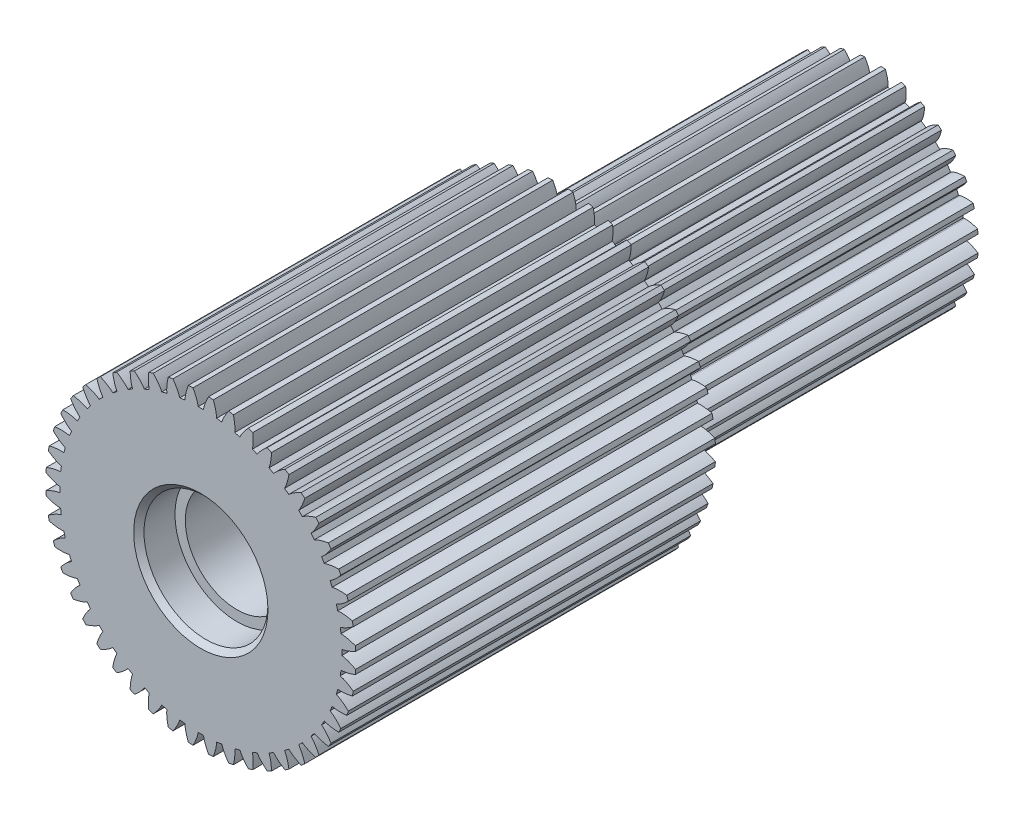
SolidWorks part; units mm, degrees
material "PLA"
ref_plane "Front Plane" through (0, 0, 0) normal (0, 0, 1) x (1, 0, 0)
ref_plane "Top Plane" through (0, 0, 0) normal (0, 1, 0) x (1, 0, 0)
ref_plane "Right Plane" through (0, 0, 0) normal (1, 0, 0) x (0, 0, -1)
sketch "Sketch1" plane through (0, 0, 0) normal (0, 0, 1) x (1, 0, 0)
  circle A0 centre (0, 0) radius 15
  dimension "D1" = 30
extrude "Boss-Extrude1" add sketch "Sketch1" along normal mid plane 34.8118
sketch "Sketch2" plane through (0, 0, 0) normal (0, 0, 1) x (1, 0, 0)
  line L0 (0, 0) -> (14.3977, 0.2566) construction
  line L1 (0, 0) -> (14.4, 0) construction
  line L2 (0, 0) -> (14.3977, -0.2566) construction
  line L3 (13.527, -0.2411) -> (13.6478, -0.2432)
  line L4 (13.5294, 0.2411) -> (13.6478, 0.2432)
  circle A0 centre (0, 0) radius 14.4 construction
  circle A1 centre (0, 0) radius 13.5316 construction
  circle A2 centre (0, 0) radius 13.65
  circle A3 centre (0, 0) radius 15 construction
  circle A4 centre (0, 0) radius 15
  spline S0 degree 4 poles (13.5294, 0.2411) (13.534, 0.2413) (13.547, 0.2419) (13.5715, 0.2439) (13.6113, 0.2483) (13.662, 0.2556) (13.7273, 0.267) (13.8039, 0.2829) (13.8878, 0.303) (13.9786, 0.3276) (14.0688, 0.3547) (14.1584, 0.3839) (14.2472, 0.4152) (14.3542, 0.4554) (14.4819, 0.507) (14.6298, 0.5722) (14.7962, 0.6518) (14.964, 0.7391) (15.1277, 0.8299) (15.2913, 0.9272) (15.4482, 1.0254) (15.6092, 1.1331) (15.7568, 1.2354) (15.9198, 1.3563) (16.0506, 1.4557) (16.2205, 1.5933) (16.32, 1.6765) (16.4355, 1.7761) (16.4863, 1.8215) (16.5176, 1.8494) knots 0 0 0 0 0 0.005377 0.015084 0.028532 0.04661 0.064855 0.092111 0.119476 0.146842 0.174209 0.201575 0.228941 0.256307 0.307035 0.361767 0.4165 0.471232 0.525964 0.580697 0.635429 0.690161 0.744894 0.799626 0.854358 0.909091 0.954545 1 1 1 1 1 construction
  spline S1 degree 4 poles (13.5294, 0.2411) (13.534, 0.2413) (13.547, 0.2419) (13.5715, 0.2439) (13.6113, 0.2483) (13.662, 0.2556) (13.7273, 0.267) (13.8039, 0.2829) (13.8878, 0.303) (13.9786, 0.3276) (14.0688, 0.3547) (14.1584, 0.3839) (14.2472, 0.4152) (14.3542, 0.4554) (14.4819, 0.507) (14.6298, 0.5722) (14.7962, 0.6518) (14.964, 0.7391) (15.1277, 0.8299) (15.2913, 0.9272) (15.4482, 1.0254) (15.6092, 1.1331) (15.7568, 1.2354) (15.9198, 1.3563) (16.0506, 1.4557) (16.1836, 1.5634) (16.2481, 1.6166) (16.2809, 1.6441) knots 0 0 0 0 0 0.005377 0.015084 0.028532 0.04661 0.064855 0.092111 0.119476 0.146842 0.174209 0.201575 0.228941 0.256307 0.307035 0.361767 0.4165 0.471232 0.525964 0.580697 0.635429 0.690161 0.744894 0.799626 0.854358 0.909091 0.909091 0.909091 0.909091 0.909091
  spline S2 degree 4 poles (13.527, -0.2411) (13.5316, -0.2412) (13.5446, -0.2419) (13.569, -0.2438) (13.6089, -0.2483) (13.6595, -0.2556) (13.7248, -0.2669) (13.8015, -0.2828) (13.8853, -0.3029) (13.9762, -0.3276) (14.0664, -0.3546) (14.1559, -0.3839) (14.2447, -0.4151) (14.3518, -0.4554) (14.4794, -0.507) (14.6274, -0.5722) (14.7937, -0.6518) (14.9616, -0.739) (15.1253, -0.8298) (15.2888, -0.9272) (15.4458, -1.0254) (15.6068, -1.1331) (15.7543, -1.2354) (15.9173, -1.3563) (16.0481, -1.4556) (16.218, -1.5932) (16.3175, -1.6764) (16.4331, -1.776) (16.4838, -1.8215) (16.5151, -1.8494) knots 0 0 0 0 0 0.005377 0.015084 0.028532 0.04661 0.064855 0.092111 0.119476 0.146842 0.174209 0.201575 0.228941 0.256307 0.307035 0.361767 0.4165 0.471232 0.525964 0.580697 0.635429 0.690161 0.744894 0.799626 0.854358 0.909091 0.954545 1 1 1 1 1 construction
  spline S3 degree 4 poles (13.527, -0.2411) (13.5316, -0.2412) (13.5446, -0.2419) (13.569, -0.2438) (13.6089, -0.2483) (13.6595, -0.2556) (13.7248, -0.2669) (13.8015, -0.2828) (13.8853, -0.3029) (13.9762, -0.3276) (14.0664, -0.3546) (14.1559, -0.3839) (14.2447, -0.4151) (14.3518, -0.4554) (14.4794, -0.507) (14.6274, -0.5722) (14.7937, -0.6518) (14.9616, -0.739) (15.1253, -0.8298) (15.2888, -0.9272) (15.4458, -1.0254) (15.6068, -1.1331) (15.7543, -1.2354) (15.9173, -1.3563) (16.0481, -1.4556) (16.1812, -1.5634) (16.2456, -1.6166) (16.2784, -1.6441) knots 0 0 0 0 0 0.005377 0.015084 0.028532 0.04661 0.064855 0.092111 0.119476 0.146842 0.174209 0.201575 0.228941 0.256307 0.307035 0.361767 0.4165 0.471232 0.525964 0.580697 0.635429 0.690161 0.744894 0.799626 0.854358 0.909091 0.909091 0.909091 0.909091 0.909091
  dimension "D1" = 28.8
  dimension "D2" = 27.0631
  dimension "D3" = 27.3
  dimension "D4" = 1.021
  dimension "D5" = 1.021
extrude "Cut-Extrude1" cut sketch "Sketch2" against normal through all both and the other way through all contours A2 A4 region at (14.4443, -0.0005, 0)
pattern_circular "CirPattern2" count 48 over 360 about axis through (0, 0, 17.4059) along (0, 0, -1) of "Cut-Extrude1"
sketch "Sketch3" plane through (0, 0, 17.4059) normal (0, 0, 1) x (1, 0, 0)
  circle A0 centre (0, 0) radius 5
  dimension "D1" = 10
sketch "Sketch4" plane through (0, 0, -17.4059) normal (0, 0, -1) x (-1, 0, 0)
  circle A0 centre (0, 0) radius 10.2
  dimension "D1" = 20.4
extrude "Boss-Extrude2" add sketch "Sketch4" along normal blind 30.2315
sketch "Sketch5" plane through (0, 0, -47.6374) normal (0, 0, -1) x (-1, 0, 0)
  line L0 (0, 0) -> (10.2, 0) construction
  line L1 (0, 0) -> (10.194, 0.3486) construction
  line L2 (0, 0) -> (10.194, -0.3486) construction
  line L3 (8.9952, 0.3076) -> (8.8448, 0.3025)
  line L4 (8.9952, -0.3076) -> (8.8448, -0.3025)
  circle A0 centre (0, 0) radius 9.021 construction
  circle A1 centre (0, 0) radius 8.85
  arc A2 (10.1694, -0.7895) -> (10.1694, 0.7895) centre (0, 0) ccw
  spline S0 degree 4 poles (8.9952, 0.3076) (8.9983, 0.3078) (9.0069, 0.3083) (9.0232, 0.3099) (9.0497, 0.3133) (9.0989, 0.3212) (9.1575, 0.3334) (9.2234, 0.3498) (9.2937, 0.3702) (9.3535, 0.3892) (9.4129, 0.4097) (9.4717, 0.4314) (9.5427, 0.4594) (9.6272, 0.4952) (9.7251, 0.5403) (9.8351, 0.5952) (9.9461, 0.6552) (10.0542, 0.7175) (10.1621, 0.7842) (10.2657, 0.8513) (10.3718, 0.9249) (10.4691, 0.9947) (10.5764, 1.077) (10.6625, 1.1447) (10.7743, 1.2383) (10.8397, 1.2948) (10.9156, 1.3625) (10.9489, 1.3933) (10.9695, 1.4123) knots 0 0 0 0 0 0.005377 0.015084 0.028532 0.04661 0.092111 0.119476 0.146842 0.174209 0.201575 0.228941 0.256307 0.307035 0.361767 0.4165 0.471232 0.525964 0.580697 0.635429 0.690161 0.744894 0.799626 0.854358 0.909091 0.954545 1 1 1 1 1 construction
  spline S1 degree 4 poles (8.9952, 0.3076) (8.9983, 0.3078) (9.0069, 0.3083) (9.0232, 0.3099) (9.0497, 0.3133) (9.0989, 0.3212) (9.1575, 0.3334) (9.2234, 0.3498) (9.2937, 0.3702) (9.3535, 0.3892) (9.4129, 0.4097) (9.4717, 0.4314) (9.5427, 0.4594) (9.6272, 0.4952) (9.7251, 0.5403) (9.8351, 0.5952) (9.9461, 0.6552) (10.0542, 0.7175) (10.1621, 0.7842) (10.2657, 0.8513) (10.3718, 0.9249) (10.4691, 0.9947) (10.5764, 1.077) (10.6625, 1.1447) (10.75, 1.218) (10.7924, 1.2541) (10.814, 1.2728) knots 0 0 0 0 0 0.005377 0.015084 0.028532 0.04661 0.092111 0.119476 0.146842 0.174209 0.201575 0.228941 0.256307 0.307035 0.361767 0.4165 0.471232 0.525964 0.580697 0.635429 0.690161 0.744894 0.799626 0.854358 0.909091 0.909091 0.909091 0.909091 0.909091
  spline S2 degree 4 poles (8.9952, -0.3076) (8.9983, -0.3078) (9.0069, -0.3083) (9.0232, -0.3099) (9.0497, -0.3133) (9.0989, -0.3212) (9.1575, -0.3334) (9.2234, -0.3498) (9.2937, -0.3702) (9.3535, -0.3892) (9.4129, -0.4097) (9.4717, -0.4314) (9.5427, -0.4594) (9.6272, -0.4952) (9.7251, -0.5403) (9.8351, -0.5952) (9.9461, -0.6552) (10.0542, -0.7175) (10.1621, -0.7842) (10.2657, -0.8513) (10.3718, -0.9249) (10.4691, -0.9947) (10.5764, -1.077) (10.6625, -1.1447) (10.7743, -1.2383) (10.8397, -1.2948) (10.9156, -1.3625) (10.9489, -1.3933) (10.9695, -1.4123) knots 0 0 0 0 0 0.005377 0.015084 0.028532 0.04661 0.092111 0.119476 0.146842 0.174209 0.201575 0.228941 0.256307 0.307035 0.361767 0.4165 0.471232 0.525964 0.580697 0.635429 0.690161 0.744894 0.799626 0.854358 0.909091 0.954545 1 1 1 1 1 construction
  spline S3 degree 4 poles (8.9952, -0.3076) (8.9983, -0.3078) (9.0069, -0.3083) (9.0232, -0.3099) (9.0497, -0.3133) (9.0989, -0.3212) (9.1575, -0.3334) (9.2234, -0.3498) (9.2937, -0.3702) (9.3535, -0.3892) (9.4129, -0.4097) (9.4717, -0.4314) (9.5427, -0.4594) (9.6272, -0.4952) (9.7251, -0.5403) (9.8351, -0.5952) (9.9461, -0.6552) (10.0542, -0.7175) (10.1621, -0.7842) (10.2657, -0.8513) (10.3718, -0.9249) (10.4691, -0.9947) (10.5764, -1.077) (10.6625, -1.1447) (10.75, -1.218) (10.7924, -1.2541) (10.814, -1.2728) knots 0 0 0 0 0 0.005377 0.015084 0.028532 0.04661 0.092111 0.119476 0.146842 0.174209 0.201575 0.228941 0.256307 0.307035 0.361767 0.4165 0.471232 0.525964 0.580697 0.635429 0.690161 0.744894 0.799626 0.854358 0.909091 0.909091 0.909091 0.909091 0.909091
  dimension "D2" = 17.7
  dimension "D3" = 20.4
  dimension "D1" = 18.0421
  dimension "D4" = 1.959
  dimension "D5" = 1.959
extrude "Cut-Extrude2" cut sketch "Sketch5" against normal up to surface (30.2315 mm away) contours A2 A1 region at (-9.6386, 0, -47.6374) up to face at (10.2, 0, -17.4059)
pattern_circular "CirPattern3" count 32 over 360 about axis through (0, 0, -47.6374) along (0, 0, 1) of "Cut-Extrude2"
extrude "Cut-Extrude3" cut sketch "Sketch3" against normal through all contours A0
sketch "Sketch7" plane through (0, 0, -47.6374) normal (0, 0, -1) x (-1, 0, 0)
  circle A0 centre (0, 0) radius 6
  dimension "D1" = 12
extrude "Cut-Extrude4" cut sketch "Sketch7" against normal blind 3.5
ref_plane "Plane1" through (0, 0, -15.1158) normal (0, 0, -1) x (-1, 0, 0)
mirror "Mirror1" about plane through (0, 0, -15.1158) normal (0, 0, -1) of "Cut-Extrude4"
chamfer "Chamfer1" distance 0.5 angle 45 2 edges at (-6, 0, 17.4059) (-6, 0, -47.6374)
equation "\"module\" = 0.6"
equation "\"pressure angle\" = 20.0"
equation "\"h_a\" = 0.6"
equation "\"h_b\" = 0.75"
equation "\"clr_tip_root\" = 0.15000000000000002"
equation "\"D1@Sketch1\" = \"dp_p_b\" + 2 * \"h_a\""
equation "\"D1@Boss-Extrude1\" = \"fw_p_b\""
equation "\"D1@Sketch2\" = \"dp_p_b\""
equation "\"D2@Sketch2\"= \"db_p_b\""
equation "\"D3@Sketch2\" = \"dp_p_b\" - 2 * \"h_b\""
equation "\"Nr_s\" = 128"
equation "\"pressure_angle\" = 20.0"
equation "\"h_f\" = 0.75"
equation "\"dp_r_s\" = 76.8"
equation "\"bearing_ID\" = 65"
equation "\"bearing_OD\" = 85"
equation "\"bearing_height\" = 10"
equation "\"clearance_planet\" = 1.5"
equation "\"case_dist\" = 6.5"
equation "\"Motor_case_OD_max\" = 131.3"
equation "\"case_mounting_PCD\" = 123.8"
equation "\"bearing mount thickness\" = 8"
equation "\"case_mounting_hole_dia\" = 3"
equation "\"output_mounting_PCD\" = 93"
equation "\"output_mounting_hole_dia\" = 4"
equation "\"clearance_case_mount_holes_shell_thickness\" = 1"
equation "\"motor_case_OD_base\" = 121.8"
equation "\"sec_carrier_thickness\" = 5"
equation "\"sun_coupler_hub_thickness\" = 4"
equation "\"clearance_sun_coupler_sec_carrier\" = 1.5"
equation "\"clearance_motor_and_case\" = 5"
equation "\"motor_OD\" = 106.8"
equation "\"Motor_case_thickness\" = 2.5"
equation "\"Motor_case_ID\" = 116.8"
equation "\"case_mounting_hole_shift\" = 1.0"
equation "\"output_mounting_nut_wrench_size\" = 7"
equation "\"output_mounting_nut_thickness\" = 3.2"
equation "\"case_mounting_hole_allen_socket_dia\" = 5.5"
equation "\"output_mounting_nut_depth\" = 3"
equation "\"case_mounting_bolt_depth\" = 4.5"
equation "\"Ns\" = 48"
equation "\"ring_radial_thickness\" = 5"
equation "\"ring_to_chamfer_clearance\" = 1.5"
equation "\"Motor_case_OD_base_to_chamfer\" = 5"
equation "\"pattern_offset_from_motor_case_OD_base\" = 3"
equation "\"pattern_bulge_dia\" = 3"
equation "\"pattern_num_bulge\" = 18"
equation "\"pattern_depth\" = 2"
equation "\"motor_height\" = 47.6"
equation "\"case_mounting_wrench_size\" = 5.5"
equation "\"case_mounting_nut_clearance\" = 2"
equation "\"base_plate_thickness\" = 4"
equation "\"case_mounting_nut_thickness\" = 2.4"
equation "\"case_mounting_surface_height\" = 4"
equation "\"motor_mount_hole_PCD\" = 40"
equation "\"motor_mount_hole_dia\" = 5"
equation "\"motor_mount_hole_num\" = 4"
equation "\"central_hole_offset_from_motor_mount_PCD\" = 5"
equation "\"wire_slot_dist_from_center\" = 45.5"
equation "\"wire_slot_length\" = 10"
equation "\"wire_slot_radius\" = 3"
equation "\"driver_upper_holes_dist_from_center\" = 29"
equation "\"driver_lower_holes_dist_from_center\" = 13"
equation "\"driver_side_holes_dist_from_center\" = 22.5"
equation "\"driver_mount_holes_dia\" = 3"
equation "\"driver_mount_inserts_OD\" = 4.8"
equation "\"driver_mount_thickness\" = 1.5"
equation "\"driver_mount_height\" = 6"
equation "\"air_flow_hole_offset\" = 3"
equation "\"num_planet\" = 4"
equation "\"planet_pin_bolt_dia\" = 5"
equation "\"planet_pin_socket_head_dia\" = 8.5"
equation "\"carrier_PCD\" = 57.599999999999994"
equation "\"planet_shaft_dia\" = 8"
equation "\"planet_shaft_step_offset\" = 1"
equation "\"carrier_trapezoidal_support_sun_offset\" = 5"
equation "\"carrier_trapezoidal_support_hole_PCD_offset_bearing_ID\" = 4"
equation "\"carrier_trapezoidal_support_hole_dia\" = 3"
equation "\"carrier_trapezoidal_support_hole_socket_head_dia\" = 5.5"
equation "\"carrier_bearing_step_width\" = 1.5"
equation "\"standard_clearance_1_5mm\" = 1.5"
equation "\"standard_fillet_1_5mm\" = 1.5"
equation "\"sun_shaft_bearing_OD\" = 16"
equation "\"sun_shaft_bearing_width\" = 5"
equation "\"standard_bearing_insertion_chamfer\" = 0.5"
equation "\"carrier_trapezoidal_support_hole_wrench_size\" = 5.5"
equation "\"planet_pin_bolt_wrench_size\" = 8"
equation "\"planet_bearing_OD\" = 12"
equation "\"planet_bearing_width\" = 3.5"
equation "\"planet_bore\" = 10"
equation "\"D1@Sketch3\"=\"planet_bore\""
equation "\"Np_b\" = 48"
equation "\"dp_s\" = 28.799999999999997"
equation "\"db_s\" = 27.06314747863416"
equation "\"fw_s_calc\" = 7.664359769718526"
equation "\"alpha_s\" = 0.8539582918412343"
equation "\"beta_s\" = 2.0420834163175314"
equation "\"dp_p_b\" = 28.799999999999997"
equation "\"db_p_b\" = 27.06314747863416"
equation "\"fw_p_s\" = 30.231545005724083"
equation "\"alpha_p_b\" = 0.8539582918412343"
equation "\"beta_p_b\" = 2.0420834163175314"
equation "\"motor_output_hole_PCD\" = 23"
equation "\"motor_output_hole_dia\" = 4"
equation "\"motor_output_hole_num\" = 4"
equation "\"sun_shaft_bearing_ID\" = 8"
equation "\"sun_hub_dia\" = 30.0"
equation "\"sun_central_bolt_dia\" = 5"
equation "\"sun_central_bolt_socket_head_dia\" = 8.5"
equation "\"fw_s_used\" = 72.54334182621932"
equation "\"motor_output_hole_CSK_OD\" = 8"
equation "\"motor_output_hole_CSK_head_height\" = 2.0"
equation "\"bearing_retainer_thickness\" = 2"
equation "\"Np_s\" = 32"
equation "\"fw_p_b\" = 34.81179682049524"
equation "\"dp_p_s\" = 19.2"
equation "\"db_p_s\" = 18.04209831908944"
equation "\"alpha_p_s\" = 0.8539582918412556"
equation "\"beta_p_s\" = 3.917083416317489"
equation "\"D1@Sketch4\"=\"dp_p_s\" + 2 * \"h_a\""
equation "\"D1@Boss-Extrude2\"=\"fw_p_s\""
equation "\"D2@Sketch5\"=\"dp_p_s\" - 2 * \"h_b\""
equation "\"D3@Sketch5\"=\"dp_p_s\"+2 * \"h_a\" "
equation "\"D1@Sketch5\"=\"db_p_s\""
equation "\"D1@CirPattern3\"=\"Np_s\""
equation "\"D4@Sketch5\"=\"beta_p_s\"/2"
equation "\"D5@Sketch5\"=\"beta_p_s\"/2"
equation "\"D4@Sketch2\"=\"beta_p_b\"/2"
equation "\"D5@Sketch2\"=\"beta_p_b\"/2"
equation "\"D1@Sketch7\"=\"planet_bearing_OD\""
equation "\"D1@Cut-Extrude4\"=\"planet_bearing_width\""
equation "\"D1@Chamfer1\"=\"standard_bearing_insertion_chamfer\""
equation "\"D1@CirPattern2\"=\"Np_b\""
equation "\"Nr_b\" = 144"
equation "\"dp_r_b\" = 86.39999999999999"
equation "\"db_r_b\" = 81.18944243590248"
equation "\"fw_r_b\" = 34.81179682049524"
equation "\"alpha_r_b\" = 0.8539582918412414"
equation "\"beta_r_b\" = 2.957916583682483"
equation "\"ring_OD_b\" = 96.39999999999999"
equation "\"Fillet10\"= IIF ( \"ring_OD_b\" > ( \"bearing_OD\" + 2 * \"bearing mount thickness\" ) , \"suppressed\" , \"unsuppressed\" )"
equation "\"Fillet11\"= IIF ( \"ring_OD_b\" < ( \"bearing_OD\" + 2 * \"bearing mount thickness\" ) , \"suppressed\" , \"unsuppressed\" )"
equation "\"clr_tip_root_s\" = 0.15000000000000002"
equation "\"db_r_s\" = 72.16839327635776"
equation "\"fw_r_s\" = 28.731545005724083"
equation "\"alpha_r_s\" = 0.8539582918412556"
equation "\"beta_r_s\" = 3.114166583682511"
equation "\"small_ring_case_thickness\" = 4"
equation "\"carrier_thickness\" = 4"
equation "\"small_ring_output_wall_thickness\" = 5"
equation "\"small_ring_output_wall_to_bearing_shaft_attachement_hole_dia\" = 4"
equation "\"small_ring_output_wall_to_bearing_shaft_attachement_hole_depth\" = 6.5"
equation "\"small_ring_output_wall_to_bearing_shaft_attachement_nut_wrench\" = 7"
equation "\"small_ring_output_wall_to_bearing_shaft_attachement_nut_thickness\" = 3.2"
equation "\"small_ring_output_wall_to_bearing_shaft_attachement_hole_pcd\" = 12"
equation "\"small_ring_output_wall_to_bearing_shaft_attachement_hole_num\" = 3"
equation "\"small_ring_output_wall_to_bearing_shaft_attachement_hole_CSK_OD\" = 8"
equation "\"small_ring_output_wall_to_bearing_shaft_attachement_hole_CSK_head_height\" = 2.0"
equation "\"carrier_small_ring_inner_bearing_ID\" = 20"
equation "\"carrier_small_ring_inner_bearing_OD\" = 32"
equation "\"carrier_small_ring_inner_bearing_height\" = 7"
equation "\"carrier_small_ring_inner_bearing_flap\" = 2"
equation "\"gear_casing_big_ring_to_bearing_dist\" = 39.23154500572409"
equation "\"gear_casing_thickness\" = 4"
